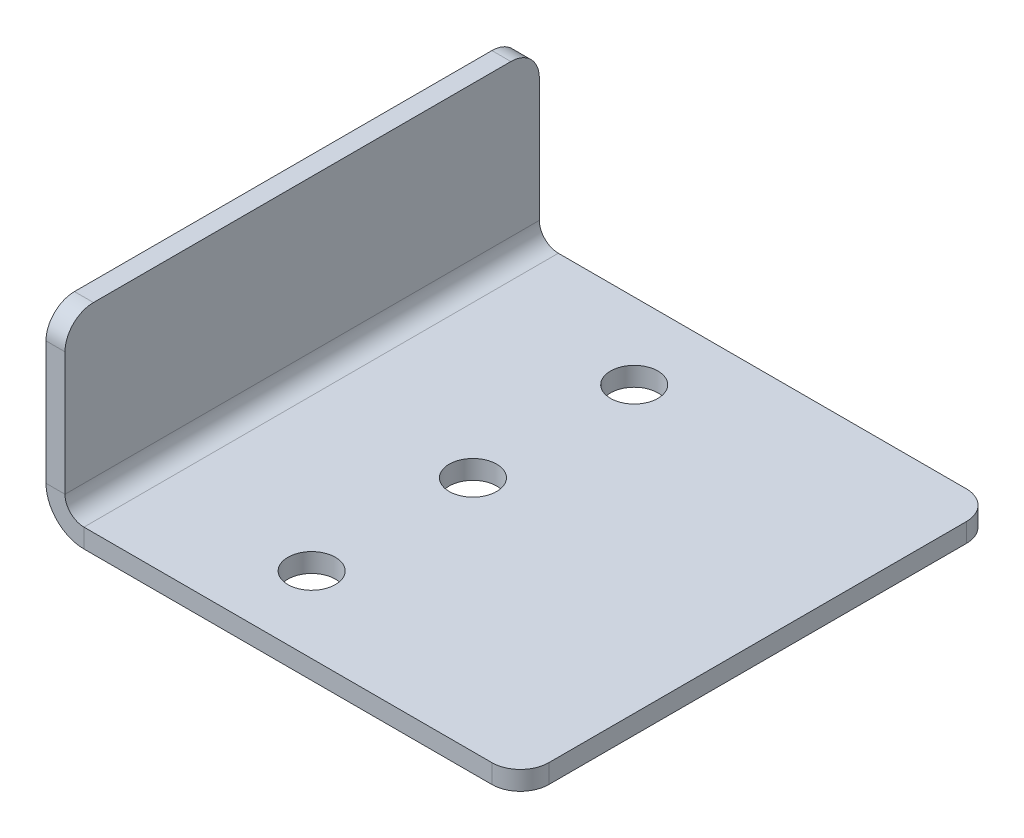
SolidWorks part; units mm, degrees
note: The reader was unsure of these and kept them because the rebuilt part matched: flange length of "Edge-Flange1".
ref_plane "Front Plane" through (0, 0, 0) normal (0, 0, 1) x (1, 0, 0)
ref_plane "Top Plane" through (0, 0, 0) normal (0, 1, 0) x (1, 0, 0)
ref_plane "Right Plane" through (0, 0, 0) normal (1, 0, 0) x (0, 0, -1)
sketch "Sketch1" plane through (0, 0, 0) normal (0, 1, 0) x (1, 0, 0)
  line L1 (25, -25) -> (-25, -25)
  line L2 (25, -25) -> (25, 25)
  line L3 (25, 25) -> (-25, 25)
  line L4 (-25, -25) -> (-25, 25)
  line L5 (25, -25) -> (-25, 25) construction
  line L6 (25, 25) -> (-25, -25) construction
  point P0 (0, 0)
  dimension "D1" = 50
  dimension "D2" = 50
base flange "Base-Flange1" sketch "Sketch1" thickness 2 reverse thickness direction yes parameters "D1"=9
edge flange "Edge-Flange1" sketch "Sketch8" flange angle 90 flange length 20 flange position material inside bend radius 2 thickness 2 relief rectangular parameters "D6"=10
sketch "Sketch8" plane through (-25, 2, 0) normal (1, 0, 0) x (0, 0, -1)
  line L2 (-25, 0) -> (-25, 18)
  line L3 (-25, 18) -> (25, 18)
  line L4 (25, 18) -> (25, 0)
  line L5 (25, 0) -> (-25, 0) construction
  line L6 (25, 0) -> (-25, 0)
bend "EdgeBend1" bend radius 2 bend angle 90 parameters "D5"=1
sketch "Sketch11" plane through (0, 2, 0) normal (0, 1, 0) x (1, 0, 0)
  line L0 (25, -25) -> (25, 25) construction
  line L1 (-21, -25) -> (25, -25) construction
  point P0 (-5, 17)
  point P2 (-5, 0)
  point P4 (-5, -17)
  dimension "D1" = 30
  dimension "D2" = 8
  dimension "D3" = 17
  dimension "D4" = 17
hole_wizard "Ø5.0mm Dowel Hole1" positions "Sketch11" profile "Sketch10" hole size "Ø5.0" standard "ISO" end condition through all
sketch "Sketch10" plane through (-5, 2, -17) normal (1, 0, 0) x (0, 0, 1)
  line L0 (0, 0) -> (0, 2)
  line L1 (0, 2) -> (2.5, 2)
  line L2 (2.5, 2) -> (2.5, 0)
  line L5 (2.5, 0) -> (0, 0)
  line L11 (0, -6.35) -> (0, 107.95) construction
  dimension "Thru Hole Dia." = 5
  dimension "Thru Hole Depth" = 2
fillet "Fillet1" radius 3 4 edges at (-24, 20, -25) (25, 1, -25) (-24, 20, 25) (25, 1, 25)
sketch "Bend-Lines1" [suppressed] plane through (0, 0, 0) normal (0, 1, 0) x (1, 0, 0)
sketch "Bounding-Box1" [suppressed] plane through (0, 0, 0) normal (0, 1, 0) x (1, 0, 0)
sheet metal parameters "Sheet-Metal1" thickness 2 parameters "D1"=9
flat pattern "Flat-Pattern1" [suppressed]
sketch "Bend-Lines2" plane through (0, 0, 0) normal (0, 1, 0) x (1, 0, 0)
sketch3d "Bounding-Box2" [suppressed]
  line L0 (-25, 25, 0) -> (-25, -25, 0) construction
  line L1 (25, 25, 0) -> (25, -25, 0) construction
  line L2 (-25, 25, 0) -> (25, 25, 0) construction
  line L3 (-25, -25, 0) -> (25, -25, 0) construction
sheet metal parameters "Sheet-Metal2" thickness 2 parameters "D1"=9
flat pattern "Flat-Pattern1"
sketch "Bend-Lines2" plane through (0, 0, 0) normal (0, -1, 0) x (-1, 0, 0)
  line L0 (23.3562, -25) -> (23.3562, 25) construction
  line L1 (23.3562, -25) -> (23.3562, 25) construction
sketch3d "Bounding-Box2" [suppressed]
  line L0 (-25, -25, 0) -> (41.7124, -25, 0) construction
  line L1 (-25, 25, 0) -> (41.7124, 25, 0) construction
  line L2 (-25, -25, 0) -> (-25, 25, 0) construction
  line L3 (41.7124, -25, 0) -> (41.7124, 25, 0) construction
bend of the flat pattern "Flatten-<EdgeBend1>1"
sheet metal parameters "Sheet-Metal3" thickness 2 parameters "D1"=9
flat pattern "Flat-Pattern1"
sketch "Bend-Lines2" plane through (0, 0, 0) normal (0, -1, 0) x (-1, 0, 0)
  line L0 (23.3562, -25) -> (23.3562, 25) construction
  line L1 (23.3562, -25) -> (23.3562, 25) construction
sketch3d "Bounding-Box2" [suppressed]
  line L0 (-25, -25, 0) -> (41.7124, -25, 0) construction
  line L1 (-25, 25, 0) -> (41.7124, 25, 0) construction
  line L2 (-25, -25, 0) -> (-25, 25, 0) construction
  line L3 (41.7124, -25, 0) -> (41.7124, 25, 0) construction
bend of the flat pattern "Flatten-<EdgeBend1>1"
